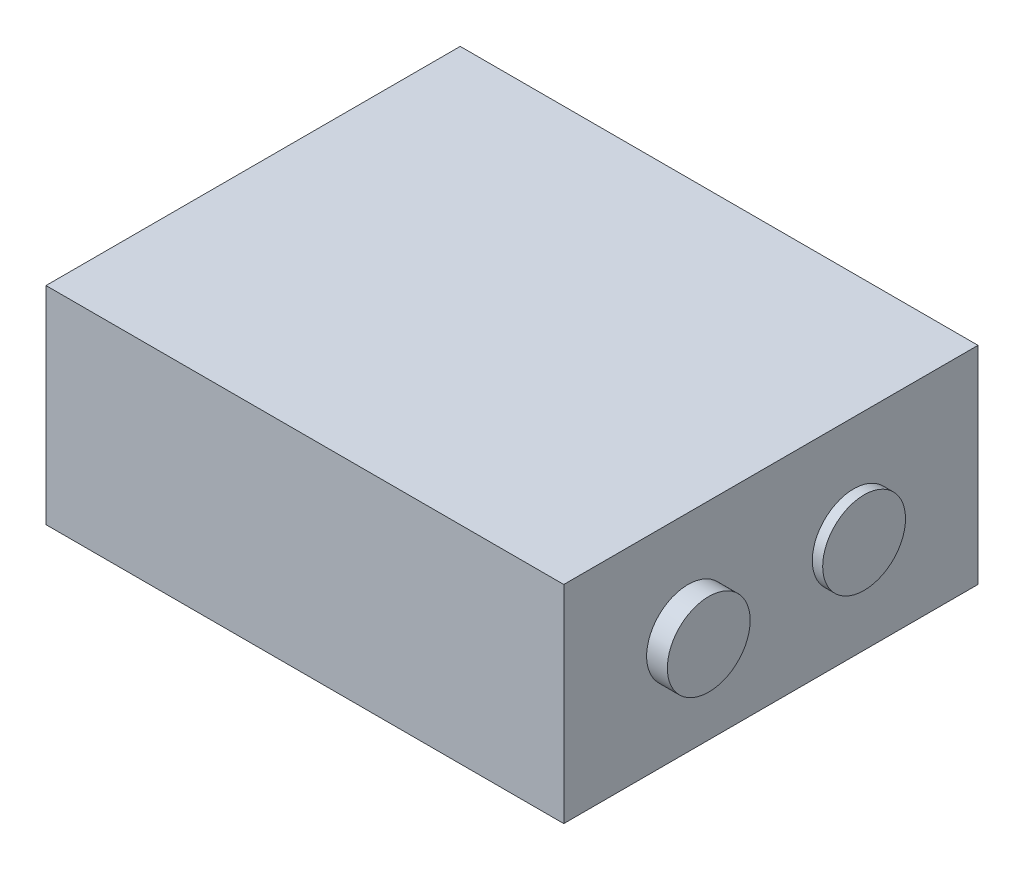
SolidWorks part; units mm, degrees
material "body"
ref_plane "前视基准面" through (0, 0, 0) normal (0, 0, 1) x (1, 0, 0)
ref_plane "上视基准面" through (0, 0, 0) normal (0, 1, 0) x (1, 0, 0)
ref_plane "右视基准面" through (0, 0, 0) normal (1, 0, 0) x (0, 0, -1)
other "质心 (COM)"
other "Configuration Table"
sketch "草图2" plane through (0, 0, 0) normal (0, 1, 0) x (1, 0, 0)
  line L1 (-250, -200) -> (250, -200)
  line L2 (-250, -200) -> (-250, 200)
  line L3 (-250, 200) -> (250, 200)
  line L4 (250, -200) -> (250, 200)
  line L5 (-250, -200) -> (250, 200) construction
  line L6 (-250, 200) -> (250, -200) construction
  point P0 (0, 0)
  dimension "D1" = 400
  dimension "D2" = 500
extrude "凸台-拉伸1" add sketch "草图2" along normal blind 200
sketch "草图3" plane through (250, 0, 0) normal (1, 0, 0) x (0, 0, -1)
  line L0 (0, 0) -> (0, 100)
  line L1 (0, 100) -> (80, 100)
  circle A0 centre (80, 100) radius 40
  circle A1 centre (-80, 100) radius 40
  dimension "D3" = 80
  dimension "D1" = 100
  dimension "D2" = 80
extrude "凸台-拉伸2" add sketch "草图3" along normal blind 10 contours A0
extrude "凸台-拉伸3" add sketch "草图3<3>" along normal blind 20 contours A1 region at (250, 100, 80)
sketch "草图3<3>" plane through (250, 0, 0) normal (1, 0, 0) x (0, 0, -1) same geometry as "草图3"
mirror "镜向1" about plane through (0, 0, 0) normal (1, 0, 0) of "凸台-拉伸3", "凸台-拉伸2"
